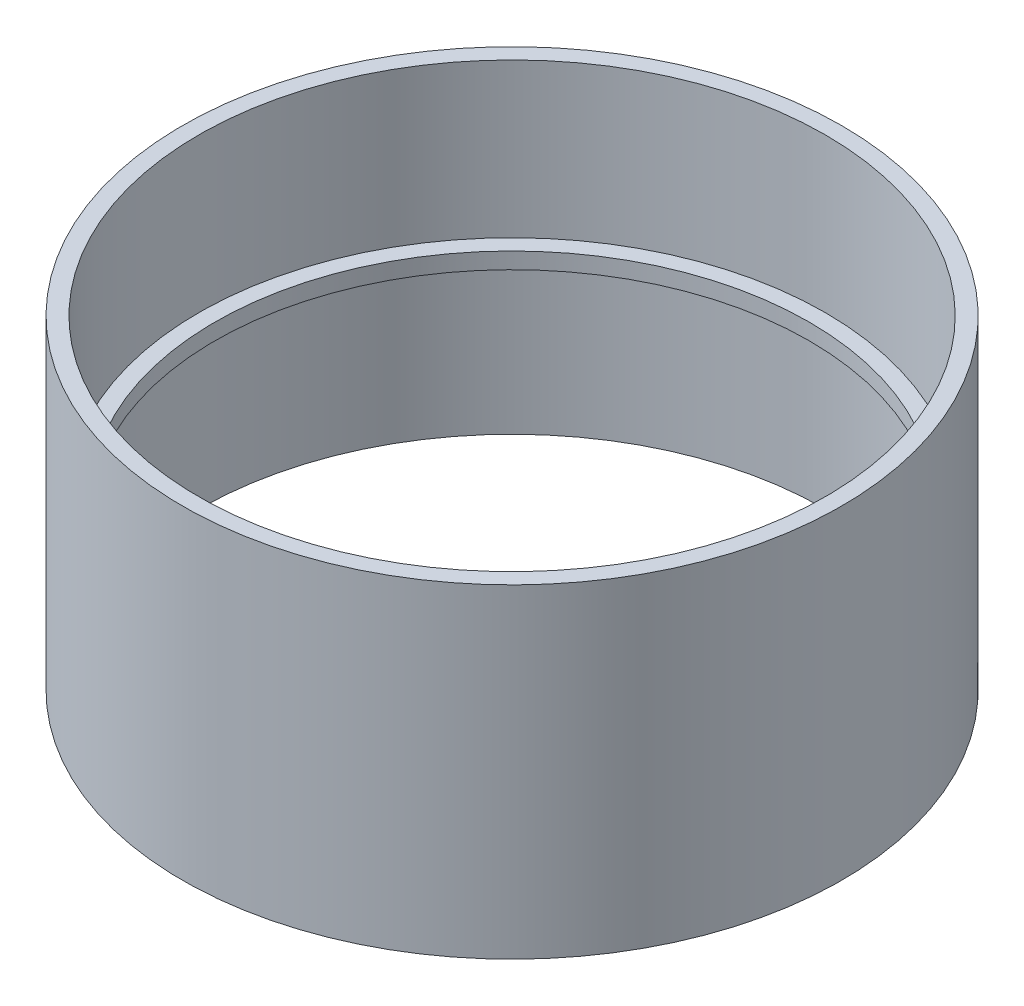
SolidWorks part; units mm, degrees
ref_plane "Front Plane" through (0, 0, 0) normal (0, 0, 1) x (1, 0, 0)
ref_plane "Top Plane" through (0, 0, 0) normal (0, 1, 0) x (1, 0, 0)
ref_plane "Right Plane" through (0, 0, 0) normal (1, 0, 0) x (0, 0, -1)
sketch "Sketch1" plane through (0, 0, 0) normal (0, 0, 1) x (1, 0, 0)
  line L0 (0, 0) -> (0, 17.5945) construction
  line L2 (29, 0) -> (30.5, 0)
  line L3 (29, 0) -> (29, 30)
  line L4 (29, 30) -> (30.5, 30)
  line L5 (30.5, 0) -> (30.5, 30)
  line L6 (29, 15.75) -> (27.5, 15.75)
  line L7 (29, 15.75) -> (29, 14.25)
  line L8 (29, 14.25) -> (27.5, 14.25)
  line L9 (27.5, 15.75) -> (27.5, 14.25)
  dimension "D1" = 30
  dimension "D2" = 1.5
  dimension "D3" = 1.5
  dimension "D4" = 1.5
  dimension "D5" = 29
  dimension "D6" = 14.25
revolve "Revolve1" add sketch "Sketch1" angle 360 about L0 region at (29.75, 15, 0) region at (28.25, 15, 0)
